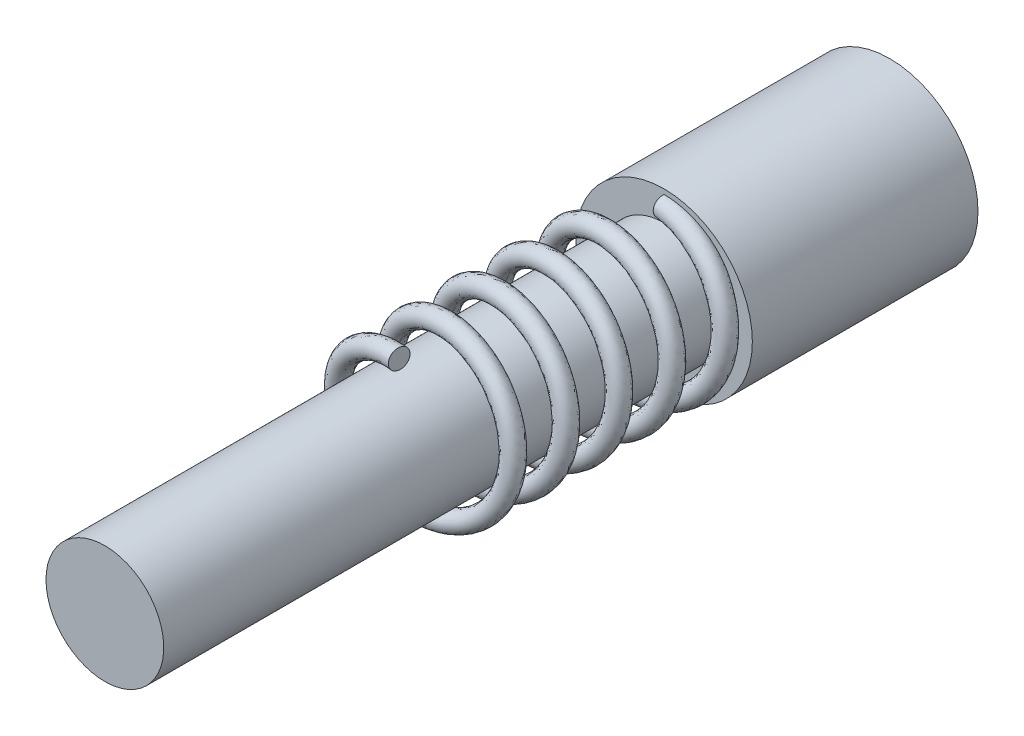
SolidWorks part; units mm, degrees
ref_plane "Front Plane" through (0, 0, 0) normal (0, 0, 1) x (1, 0, 0)
ref_plane "Top Plane" through (0, 0, 0) normal (0, 1, 0) x (1, 0, 0)
ref_plane "Right Plane" through (0, 0, 0) normal (1, 0, 0) x (0, 0, -1)
sketch "Sketch1" plane through (0, 0, 0) normal (0, 0, 1) x (1, 0, 0)
  circle A0 centre (0, 0) radius 4.5
  dimension "D1" = 9
extrude "Boss-Extrude2" add sketch "Sketch1" along normal blind 11.5
sketch "Sketch16" plane through (0, 0, 11.5) normal (0, 0, 1) x (1, 0, 0)
  circle A0 centre (0, 0) radius 3
  dimension "D1" = 6
extrude "Boss-Extrude3" add sketch "Sketch16" along normal blind 28.5
sketch "Sketch18" plane through (0, 0, 11.5) normal (0, 0, 1) x (1, 0, 0)
  circle A1 centre (0, 0) radius 3.75
  dimension "D1" = 7.5
curve "Helix/Spiral3" pitch 2.7 height 13.5 radius 3.75 left hand yes centre (0, 0, 11.5) axis (0, 0, 1) start towards (0, 1, 0)
sweep "Sweep2" add path "Helix/Spiral3" circular profile diameter 1 parameters "D3"=1
